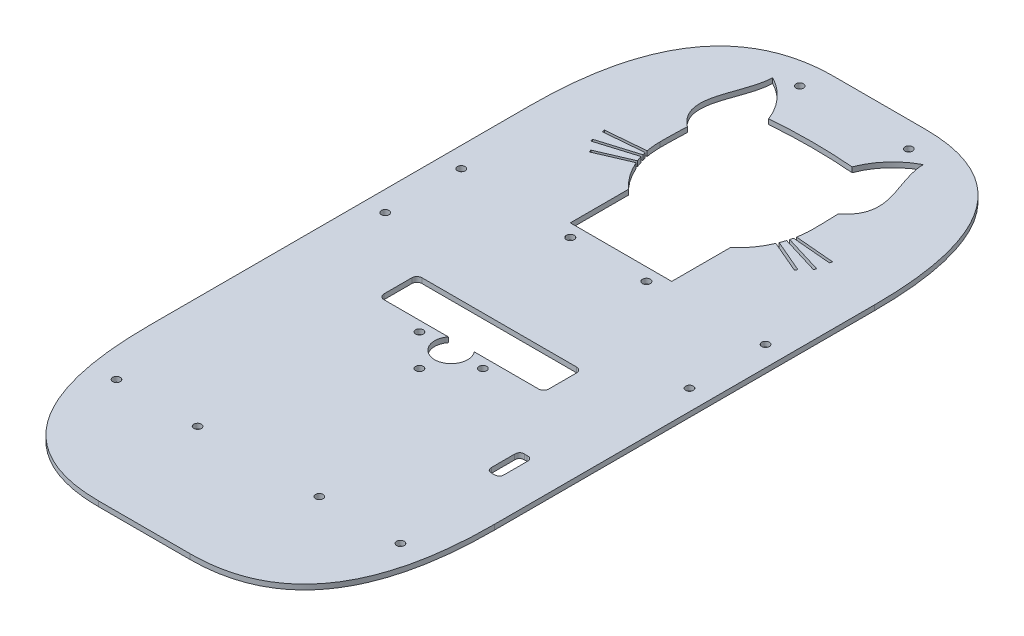
SolidWorks part; units mm, degrees
ref_plane "Спереди" through (0, 0, 0) normal (0, 0, 1) x (1, 0, 0)
ref_plane "Сверху" through (0, 0, 0) normal (0, 1, 0) x (1, 0, 0)
ref_plane "Справа" through (0, 0, 0) normal (1, 0, 0) x (0, 0, -1)
sketch "Эскиз1" plane through (0, 0, 0) normal (0, 1, 0) x (1, 0, 0)
  line L0 (0, 160) -> (0, -130) construction
  line L1 (-68, 160) -> (68, 160)
  line L2 (-68, 160) -> (-68, -130)
  line L3 (-68, -130) -> (68, -130)
  line L4 (68, 160) -> (68, -130)
  line L5 (-68, 0) -> (68, 0) construction
  dimension "D1" = 136
  dimension "D2" = 160
  dimension "D3" = 130
extrude "тело" add sketch "Эскиз1" along normal blind 2
sketch "Эскиз12" plane through (0, 2, 0) normal (0, 1, 0) x (1, 0, 0)
  line L0 (0, 160) -> (0, -130) construction
  line L1 (68, 160) -> (-68, 160) construction
  line L2 (-68, -130) -> (68, -130) construction
  line L3 (60, 55) -> (60, 25) construction
  line L4 (60, 40) -> (-60, 40) construction
  line L5 (-60, 55) -> (-60, 25) construction
  circle A0 centre (60, 55) radius 1.5
  circle A1 centre (-60, 55) radius 1.5
  circle A2 centre (-60, 25) radius 1.5
  circle A3 centre (60, 25) radius 1.5
  point P12 (-60, 40)
  point P17 (0, 40)
  dimension "D2" = 3
  dimension "D1" = 30
  dimension "D3" = 60
  dimension "D4" = 40
extrude "крепление подвески" cut sketch "Эскиз12" against normal through all
sketch "Эскиз8" plane through (0, 2, 0) normal (0, 1, 0) x (1, 0, 0)
  line L0 (-20, -130) -> (20, -130) construction
  line L1 (0, -130) -> (0, 160) construction
  line L2 (-68, -130) -> (68, -130) construction
  line L3 (68, 160) -> (-68, 160) construction
  circle A0 centre (-20, -130) radius 1.5
  circle A1 centre (20, -130) radius 1.5
  point P10 (0, -130)
  dimension "D1" = 3
  dimension "D2" = 40
  dimension "D3" = 130
extrude "крепление камеры" [suppressed] cut sketch "Эскиз8" against normal through all and the other way through all
sketch "Эскиз13" plane through (0, 2, 0) normal (0, 1, 0) x (1, 0, 0)
  line L0 (0, 160) -> (0, -130) construction
  line L1 (68, 160) -> (-68, 160) construction
  line L2 (-68, -130) -> (68, -130) construction
  line L3 (-57, 125) -> (57, 125) construction
  line L4 (-68, 15) -> (68, 15) construction
  line L5 (-57, -10) -> (57, -10) construction
  line L6 (-68, 160) -> (-68, -130) construction
  line L7 (-57, -85) -> (57, -85) construction
  line L8 (68, -130) -> (68, 160) construction
  line L9 (-25, 125) -> (-57, 125) construction
  line L10 (25, 125) -> (57, 125) construction
  line L11 (-57, -10) -> (-25, -10) construction
  line L12 (25, -10) -> (57, -10) construction
  line L13 (-57, -85) -> (-25, -85) construction
  line L14 (25, -85) -> (57, -85) construction
  circle A0 centre (-57, 125) radius 1.5
  circle A1 centre (57, 125) radius 1.5
  circle A2 centre (57, -10) radius 1.5
  circle A3 centre (-57, -10) radius 1.5
  circle A4 centre (-57, -85) radius 1.5
  circle A5 centre (57, -85) radius 1.5
  circle A6 centre (-25, 125) radius 1.5
  circle A7 centre (25, 125) radius 1.5
  circle A8 centre (25, -10) radius 1.5
  circle A9 centre (-25, -10) radius 1.5
  circle A10 centre (-25, -85) radius 1.5
  circle A11 centre (25, -85) radius 1.5
  point P18 (0, 125)
  point P19 (0, -10)
  point P20 (0, -85)
  point P27 (0, 15)
  dimension "D1" = 3
  dimension "D2" = 110
  dimension "D3" = 25
  dimension "D4" = 100
  dimension "D5" = 114
  dimension "D6" = 32
  dimension "D7" = 32
  dimension "D8" = 32
  dimension "D9" = 32
  dimension "D10" = 32
  dimension "D11" = 32
extrude "крепления уголков" [suppressed] cut sketch "Эскиз13" against normal through all
sketch "Эскиз9" plane through (0, 2, 0) normal (0, 1, 0) x (1, 0, 0)
  line L0 (0, -50) -> (0, 50) construction
  line L2 (-68, -130) -> (68, -130) construction
  circle A0 centre (0, -9) radius 6.5
  circle A1 centre (0, -9) radius 12.5 construction
  circle A2 centre (0, 3.5) radius 1.5
  circle A3 centre (12.5, -9) radius 1.5
  circle A4 centre (-12.5, -9) radius 1.5
  circle A5 centre (0, -21.5) radius 1.5
  dimension "D2" = 13
  dimension "D3" = 25
  dimension "D4" = 3
  dimension "D1" = 121
extrude "ось вращения качалки" cut sketch "Эскиз9" against normal through all
sketch "Эскиз5" plane through (0, 2, 0) normal (0, 1, 0) x (1, 0, 0)
  line L0 (-50, -65) -> (50, -25) construction
  line L1 (-50, -25) -> (50, -25) construction
  line L2 (-50, -25) -> (-50, -65) construction
  line L3 (-50, -65) -> (50, -65) construction
  line L4 (50, -25) -> (50, -65) construction
  line L5 (-50, -25) -> (50, -65) construction
  line L6 (-68, -130) -> (68, -130) construction
  circle A0 centre (-50, -25) radius 1.5
  circle A1 centre (50, -25) radius 1.5
  circle A2 centre (50, -65) radius 1.5
  circle A3 centre (-50, -65) radius 1.5
  point P12 (0, -45)
  dimension "D1" = 3
  dimension "D2" = 100
  dimension "D3" = 40
  dimension "D4" = 65
extrude "крепление raspberry" [suppressed] cut sketch "Эскиз5" against normal through all
sketch "Эскиз11" plane through (0, 2, 0) normal (0, 1, 0) x (1, 0, 0)
  line L0 (-32.5, 2.5) -> (32.5, 2.5) construction
  line L1 (-32.5, 10) -> (32.5, 10)
  line L2 (-32.5, 10) -> (-32.5, -5)
  line L3 (-32.5, -5) -> (32.5, -5)
  line L4 (32.5, 10) -> (32.5, -5)
  point P11 (0, 10)
  dimension "D1" = 65
  dimension "D2" = 15
extrude "отверстие под провода на нижний этаж" cut sketch "Эскиз11" against normal through all
fillet "Скругление3" radius 2 4 edges at (-32.5, 1, 5) (32.5, 1, 5) (32.5, 1, -10) (-32.5, 1, -10)
sketch "Эскиз14" [suppressed] plane through (0, 2, 0) normal (0, 1, 0) x (1, 0, 0)
  line L0 (0, 160) -> (0, -130) construction
  line L1 (68, 160) -> (-68, 160) construction
  line L2 (-68, -130) -> (68, -130) construction
  line L3 (-47.5, -125) -> (47.5, -125) construction
  line L4 (47.5, -115) -> (47.5, -135) construction
  line L5 (-12.5, -95) -> (12.5, -95) construction
  line L6 (-47.5, -115) -> (-47.5, -135) construction
  circle A0 centre (-47.5, -115) radius 1.5
  circle A1 centre (-47.5, -135) radius 1.5
  circle A2 centre (47.5, -115) radius 1.5
  circle A3 centre (47.5, -135) radius 1.5
  point P8 (0, -125)
  point P14 (-47.5, -125)
  point P15 (47.5, -125)
  dimension "D1" = 3
  dimension "D2" = 20
  dimension "D3" = 30
  dimension "D4" = 95
extrude "крепление стопоров" [suppressed] cut sketch "Эскиз14" against normal through all
sketch "Эскиз15" plane through (0, 2, 0) normal (0, 1, 0) x (1, 0, 0)
  line L0 (-21.5, 150) -> (21.5, 150) construction
  line L1 (68, 160) -> (-68, 160) construction
  circle A0 centre (21.5, 150) radius 1.5
  circle A1 centre (-21.5, 150) radius 1.5
  point P6 (0, 150)
  dimension "D1" = 3
  dimension "D2" = 10
  dimension "D3" = 43
extrude "Крепление фронтальной камеры" cut sketch "Эскиз15" against normal up to next
sketch "Эскиз16" plane through (0, 2, 0) normal (0, 1, 0) x (1, 0, 0)
  line L0 (-56, -85) -> (-24, -85) construction
  line L1 (-68, -130) -> (68, -130) construction
  line L2 (-68, 160) -> (-68, -130) construction
  line L3 (0, -130) -> (0, 160) construction
  line L4 (68, 160) -> (-68, 160) construction
  circle A0 centre (-56, -85) radius 1.5
  circle A1 centre (-24, -85) radius 1.5
  circle A2 centre (24, -85) radius 1.5
  circle A3 centre (56, -85) radius 1.5
  dimension "D1" = 32
  dimension "D4" = 3
  dimension "D2" = 45
  dimension "D3" = 12
extrude "Крепление силовых уголков со стороны буллета" cut sketch "Эскиз16" against normal up to next
sketch "Эскиз17" plane through (0, 2, 0) normal (0, 1, 0) x (1, 0, 0)
  line L1 (48, -30) -> (53, -30)
  line L2 (48, -30) -> (48, -43)
  line L3 (48, -43) -> (53, -43)
  line L4 (53, -30) -> (53, -43)
  dimension "D2" = 13
  dimension "D3" = 5
extrude "Отверстие по дпитание сервоприводов и шилда" cut sketch "Эскиз17" against normal up to next
sketch "Эскиз18" plane through (0, 2, 0) normal (0, 1, 0) x (1, 0, 0)
  line L0 (0, 0) -> (0, 160) construction
  line L1 (68, 160) -> (-68, 160) construction
  line L2 (-20, 58) -> (20, 58)
  line L3 (20, 58) -> (20, 81)
  line L5 (-20, 81) -> (-20, 58)
  line L6 (10, 58) -> (10, 43)
  line L7 (10, 43) -> (-10, 43)
  line L8 (-10, 43) -> (-10, 58)
  line L9 (28.2843, 93.3607) -> (-28.2843, 93.3607)
  line L11 (-29.2696, 96.7813) -> (-44.8695, 95.4286)
  line L12 (15, 53) -> (-15, 53) construction
  line L13 (-28.6963, 94.613) -> (-43.9353, 89.9676)
  line L16 (-27.5654, 91.5223) -> (-40.4203, 86.0016)
  line L17 (-29.474, 97.7673) -> (-44.9559, 96.4249)
  line L18 (-28.972, 95.5744) -> (-44.2269, 90.9242)
  line L19 (-27.9447, 92.4477) -> (-40.8149, 86.9204)
  line L20 (-44.9559, 96.4249) -> (-44.8695, 95.4286)
  line L21 (-44.2269, 90.9242) -> (-43.9353, 89.9676)
  line L22 (-40.8149, 86.9204) -> (-40.4203, 86.0016)
  line L23 (-29.356, 97.7776) -> (-44.9559, 96.4249) construction
  line L24 (-28.6804, 94.6179) -> (-43.9353, 89.9676) construction
  line L25 (-27.5501, 91.5289) -> (-40.4203, 86.0016) construction
  line L26 (40.8149, 86.9204) -> (40.4203, 86.0016)
  line L27 (44.2269, 90.9242) -> (43.9353, 89.9676)
  line L28 (44.9559, 96.4249) -> (44.8695, 95.4286)
  line L29 (27.9447, 92.4477) -> (40.8149, 86.9204)
  line L30 (28.972, 95.5744) -> (44.2269, 90.9242)
  line L31 (29.474, 97.7673) -> (44.9559, 96.4249)
  line L32 (27.5654, 91.5223) -> (40.4203, 86.0016)
  line L33 (28.6963, 94.613) -> (43.9353, 89.9676)
  line L34 (29.2696, 96.7813) -> (44.8695, 95.4286)
  arc A0 (20, 81) -> (-20, 81) centre (0, 103.3607) ccw construction
  circle A1 centre (15, 53) radius 1.55
  circle A2 centre (-15, 53) radius 1.55
  arc A4 (-30, 103.3607) -> (-28.2843, 131.3607) centre (199.3322, 103.3607) cw
  arc A5 (-28.2843, 131.3607) -> (28.2843, 131.3607) centre (0, -67.6393) cw
  arc A6 (28.2843, 131.3607) -> (30, 103.3607) centre (-199.3322, 103.3607) cw
  arc A7 (-20, 81) -> (-27.5654, 91.5223) centre (0, 103.3607) cw
  arc A8 (20, 81) -> (27.5654, 91.5223) centre (0, 103.3607) ccw
  arc A9 (29.474, 97.7673) -> (30, 103.3607) centre (0, 103.3607) ccw
  arc A10 (-29.7135, 147.5209) -> (-16.4423, 132.687) centre (-42.569, 122.6661) cw
  arc A11 (29.7135, 147.5209) -> (16.4423, 132.687) centre (42.569, 122.6661) ccw
  arc A12 (28.972, 95.5744) -> (29.2696, 96.7813) centre (0, 103.3607) ccw
  arc A13 (27.9447, 92.4477) -> (28.6963, 94.613) centre (0, 103.3607) ccw
  arc A14 (-27.9447, 92.4477) -> (-28.6963, 94.613) centre (0, 103.3607) cw
  arc A15 (-28.972, 95.5744) -> (-29.2696, 96.7813) centre (0, 103.3607) cw
  arc A16 (-29.474, 97.7673) -> (-30, 103.3607) centre (0, 103.3607) cw
  spline S0 degree 3 poles (-29.7571, 113.9123) (-42.1018, 123.5014) (-29.7562, 136.265) (-29.7135, 147.5209) knots 0 0 0 0 1 1 1 1
  spline S1 degree 3 poles (29.7571, 113.9123) (42.1018, 123.5014) (29.7562, 136.265) (29.7135, 147.5209) knots 0 0 0 0 1 1 1 1
  point P9 (0, 43)
  point P15 (0, 58)
  point P25 (0, 53)
  dimension "D6" = 60
  dimension "D8" = 3.1
  dimension "D1" = 40
  dimension "D2" = 20
  dimension "D3" = 15
  dimension "D4" = 23
  dimension "D5" = 10
  dimension "D9" = 5
  dimension "D10" = 30
  dimension "D11" = 38
  dimension "D12" = 56.5685
  dimension "D13" = 1
  dimension "D14" = 1
  dimension "D15" = 1
fillet "Скругление4" radius 50 2 edges at (68, 1, 130) (-68, 1, -160) second distance 70 conic rho 0.5 first distance on face at (0, 1, 130) first distance on face at (0, 1, -160)
fillet "Скругление5" radius 70 2 edges at (-68, 1, 130) (68, 1, -160) second distance 50 conic rho 0.5 first distance on face at (-68, 1.25, -35) first distance on face at (68, 1.25, 5)
fillet "Скругление6" radius 2 4 edges at (48, 1, 43) (53, 1, 43) (48, 1, 30) (53, 1, 30) conic rho 0.5
sketch "Эскиз19" plane through (0, 2, 0) normal (0, 1, 0) x (1, 0, 0)
  line L1 (-95.3857, 162.9355) -> (76.7354, 162.9355)
  line L2 (-95.3857, 162.9355) -> (-95.3857, 60)
  line L3 (-95.3857, 60) -> (76.7354, 60)
  line L4 (76.7354, 162.9355) -> (76.7354, 60)
  circle A0 centre (-60, 55) radius 1.5 construction
  dimension "D1" = 5
extrude "Вырез-Вытянуть3" [suppressed] cut sketch "Эскиз19" against normal up to next
fillet "Скругление8" [suppressed] radius 10
extrude "Вырез под манипулятор" cut sketch "Эскиз18" against normal up to next contours S0 A4 A5 A10 | A6 S1 A11 A5 | A16 L17 L20 L11 A15 L18 L21 L13 A14 L9 A13 L33 L27 L30 A12 L34 L28 L31 A9 A6 A5 A4 | A14 L19 L22 L16 A7 L5 L2 L3 A8 L32 L26 L29 A13 L9 | A1 | A2 region at (0, 2, -76.9456) region at (0, 2, -112.4371) region at (-27.968, 2, -132.7806) region at (27.968, 2, -132.7806) region at (15, 2, -53) region at (-15, 2, -53)
